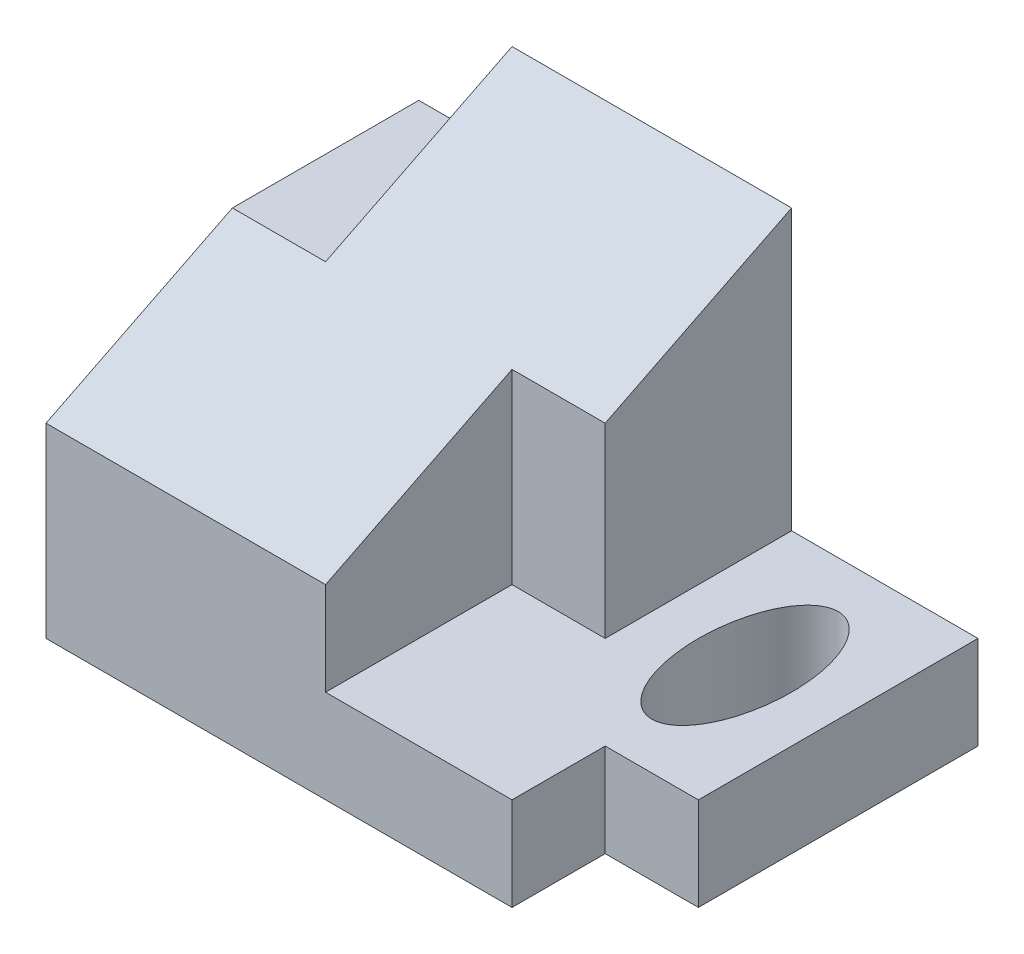
SolidWorks part; units mm, degrees
ref_plane "Front Plane" through (0, 0, 0) normal (0, 0, 1) x (1, 0, 0)
ref_plane "Top Plane" through (0, 0, 0) normal (0, 1, 0) x (1, 0, 0)
ref_plane "Right Plane" through (0, 0, 0) normal (1, 0, 0) x (0, 0, -1)
sketch "Sketch2" plane through (0, 0, 0) normal (0, 0, 1) x (1, 0, 0)
  line L1 (-76.2, -50.8) -> (76.2, -50.8)
  line L2 (-76.2, -50.8) -> (-76.2, 50.8)
  line L3 (-76.2, 50.8) -> (76.2, 50.8)
  line L4 (76.2, -50.8) -> (76.2, 50.8)
  line L5 (-76.2, -50.8) -> (76.2, 50.8) construction
  line L6 (-76.2, 50.8) -> (76.2, -50.8) construction
  point P0 (0, 0)
  dimension "D1" = 152.4
  dimension "D2" = 101.6
extrude "Boss-Extrude1" add sketch "Sketch2" along normal mid plane 101.6
sketch "Sketch3" plane through (0, 0, 50.8) normal (0, 0, 1) x (1, 0, 0)
  line L0 (-76.2, -50.8) -> (76.2, -50.8) construction
  line L1 (76.2, 50.8) -> (25.4, 50.8)
  line L2 (76.2, 50.8) -> (76.2, -25.4)
  line L3 (76.2, -25.4) -> (25.4, -25.4)
  line L4 (25.4, 50.8) -> (25.4, -25.4)
  line L5 (76.2, 50.8) -> (25.4, -25.4) construction
  line L6 (76.2, -25.4) -> (25.4, 50.8) construction
  point P4 (50.8, 12.7)
  dimension "D1" = 25.4
  dimension "D2" = 50.8
extrude "Cut-Extrude1" cut sketch "Sketch3" against normal through all
sketch "Sketch4" plane through (0, -25.4, 0) normal (0, 1, 0) x (1, 0, 0)
  line L1 (76.2, -50.8) -> (50.8, -50.8)
  line L2 (76.2, -50.8) -> (76.2, -25.4)
  line L3 (76.2, -25.4) -> (50.8, -25.4)
  line L4 (50.8, -50.8) -> (50.8, -25.4)
  line L5 (76.2, -50.8) -> (50.8, -25.4) construction
  line L6 (76.2, -25.4) -> (50.8, -50.8) construction
  point P4 (63.5, -38.1)
  dimension "D1" = 25.4
  dimension "D2" = 25.4
extrude "Cut-Extrude2" cut sketch "Sketch4" against normal through all
sketch "Sketch5" plane through (0, 50.8, 0) normal (0, 1, 0) x (1, 0, 0)
  line L1 (25.4, -50.8) -> (0, -50.8)
  line L2 (25.4, -50.8) -> (25.4, 0)
  line L3 (25.4, 0) -> (0, 0)
  line L4 (0, -50.8) -> (0, 0)
  line L5 (25.4, -50.8) -> (0, 0) construction
  line L6 (25.4, 0) -> (0, -50.8) construction
  point P4 (12.7, -25.4)
  dimension "D1" = 0
  dimension "D2" = 25.4
extrude "Cut-Extrude3" cut sketch "Sketch5" against normal up to surface (76.2 mm away) up to face at (50.8, -25.4, 8.4667)
sketch "Sketch6" plane through (0, 0, -50.8) normal (0, 0, -1) x (-1, 0, 0)
  line L1 (76.2, 50.8) -> (50.8, 50.8)
  line L2 (76.2, 50.8) -> (76.2, 25.4)
  line L3 (76.2, 25.4) -> (50.8, 25.4)
  line L4 (50.8, 50.8) -> (50.8, 25.4)
  line L5 (76.2, 50.8) -> (50.8, 25.4) construction
  line L6 (76.2, 25.4) -> (50.8, 50.8) construction
  point P4 (63.5, 38.1)
  dimension "D1" = 25.4
  dimension "D2" = 25.4
extrude "Cut-Extrude4" cut sketch "Sketch6" against normal through all
chamfer "Chamfer1" distance 101.6 distance2 50.8 1 edges at (-25.4, 50.8, 50.8) first distance on face at (-8.4667, 50.8, 0)
sketch "Sketch7" plane through (0, -25.4, 0) normal (0, 1, 0) x (1, 0, 0)
  line L0 (76.2, 50.8) -> (76.2, -25.4) construction
  ellipse E0 centre (50.8, 12.7) end of major axis (50.8, -12.7) minor radius 12.7
  dimension "D1" = 12.7
  dimension "D2" = 25.4
  dimension "D3" = 12.7
  dimension "D4" = 38.1
extrude "Cut-Extrude5" cut sketch "Sketch7" against normal through all
